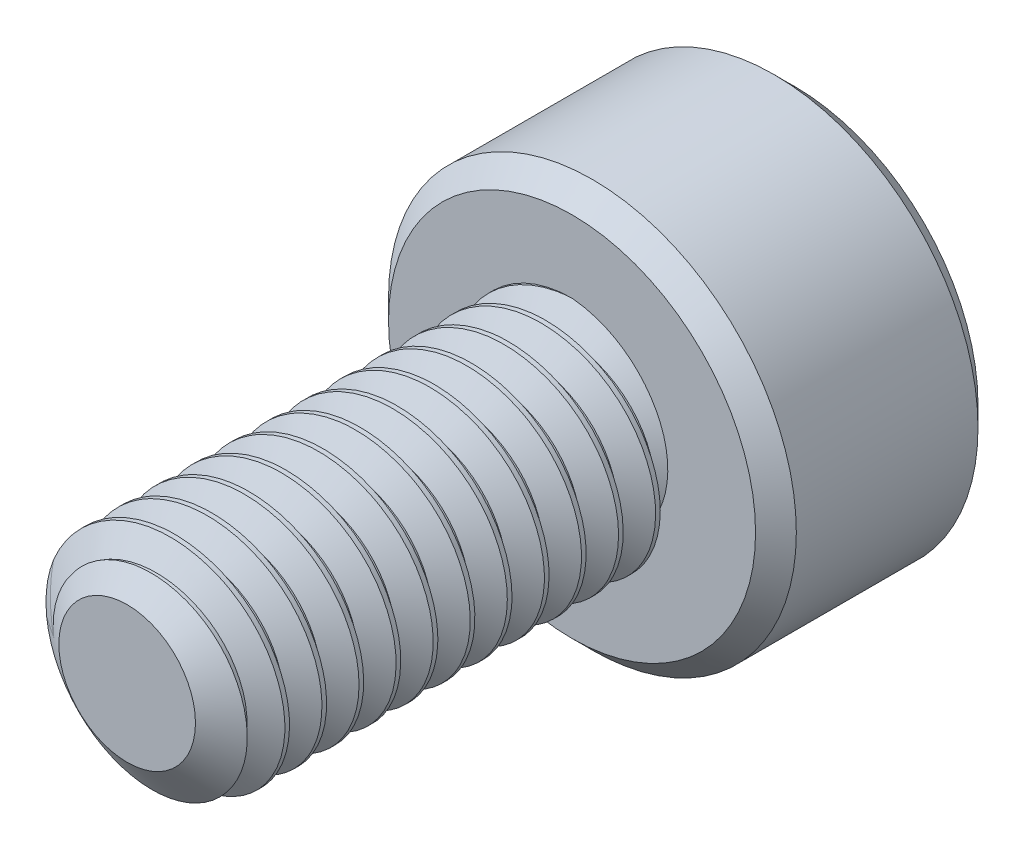
SolidWorks part; units mm, degrees
ref_plane "Front Plane" through (0, 0, 0) normal (0, 0, 1) x (1, 0, 0)
ref_plane "Top Plane" through (0, 0, 0) normal (0, 1, 0) x (1, 0, 0)
ref_plane "Right Plane" through (0, 0, 0) normal (1, 0, 0) x (0, 0, -1)
sketch "Sketch1" plane through (0, 0, 0) normal (0, 0, 1) x (1, 0, 0)
  circle A0 centre (0, 0) radius 1.5
  dimension "OD" = 3
extrude "Extrude1" add sketch "Sketch1" against normal blind 6
sketch "Sketch2" plane through (0, 0, 0) normal (0, 0, 1) x (1, 0, 0)
  circle A0 centre (0, 0) radius 1.5 construction
  circle A1 centre (0, 0) radius 1.5
curve "Helix/Spiral1" pitch 0.5 height 6.5 radius 1.5 centre (0, 0, 0) axis (0, 0, -1) start towards (0, 1, 0) parameters "pitch"=0.5
sketch "Sketch3" plane through (0, 0, 0) normal (1, 0, 0) x (0, 0, -1)
  line L0 (-0.4375, 1.5) -> (-0.25, 1.1752)
  line L1 (-0.25, 1.1752) -> (-0.1875, 1.1752)
  line L2 (-0.1875, 1.1752) -> (0, 1.5)
  line L3 (-0.4375, 1.5) -> (0, 1.5)
  line L4 (-0.2187, 1.5) -> (-0.2188, 1.1752) construction
  line L5 (-0.3438, 1.3376) -> (-0.0938, 1.3376) construction
  line L6 (0, 1.5) -> (0, -1.5) construction
  dimension "D1" = 0.0625
  dimension "D2" = 0.25
  dimension "D3" = 60
sweep "Cut-Sweep1" cut profiles "Sketch3" path "Helix/Spiral1" align with end faces yes
sketch "Sketch4" plane through (0, 0, 0) normal (1, 0, 0) x (0, 0, -1)
  line L0 (0.4053, 1.5) -> (0, 0.9212)
  line L1 (0, 0.9212) -> (0, 1.5)
  line L2 (0.4053, 1.5) -> (0, 1.5)
  line L3 (-0.4375, 1.5) -> (0, 1.5) construction
  line L4 (0, 0) -> (7.0209, 0) construction
  dimension "D1" = 55
  dimension "D2" = 0.254
revolve "Cut-Revolve1" cut sketch "Sketch4" angle 360 about L4
sketch "Sketch6" plane through (0, 0, -6) normal (0, 0, -1) x (-1, 0, 0)
  circle A0 centre (0, 0) radius 2.75
  dimension "head dia" = 5.5
extrude "Extrude2" add sketch "Sketch6" along normal blind 3
sketch "Sketch7" plane through (0, 0, -9) normal (0, 0, -1) x (-1, 0, 0)
  line L1 (0, 1.4434) -> (-1.25, 0.7217)
  line L2 (-1.25, 0.7217) -> (-1.25, -0.7217)
  line L3 (-1.25, -0.7217) -> (0, -1.4434)
  line L4 (0, -1.4434) -> (1.25, -0.7217)
  line L5 (1.25, -0.7217) -> (1.25, 0.7217)
  line L6 (1.25, 0.7217) -> (0, 1.4434)
  circle A0 centre (0, 0) radius 1.25 construction
  dimension "hex dia" = 2.5
extrude "Cut-Extrude1" cut sketch "Sketch7" against normal blind 1.875
sketch "Sketch8" plane through (0, 0, -9) normal (0, 0, -1) x (-1, 0, 0)
  circle A0 centre (0, 0) radius 1.4434
extrude "Cut-Extrude2" cut sketch "Sketch8" against normal through all draft 45
chamfer "Chamfer1" distance 0.275 angle 45 2 edges at (-2.75, 0, -9) (-2.75, 0, -6)
sketch "Sketch10" plane through (0, 0, -6) normal (0, 0, 1) x (1, 0, 0)
  circle A1 centre (0, 0) radius 1.5
  circle A2 centre (0, 0) radius 1.5
  dimension "D1" = 0
ref_plane "Plane1" through (0, 0, 0) normal (0, 0, 1) x (1, 0, 0)
extrude "partial thread" [suppressed] add sketch "Sketch10" along normal up to surface (4 mm away) separate body up to plane "Plane1"
chamfer "Chamfer2" [suppressed] distance 0.06 angle 45
combine bodies "Combine1" [suppressed] operation type add bodies to combine 107 108
sketch "Sketch9" plane through (0, 0, 0) normal (1, 0, 0) x (0, 0, -1)
  line L0 (0, 1.5) -> (0, -1.5) construction
  line L1 (1.25, 1.5) -> (1.25, -1.5) construction
  dimension "D1" = 1.25
equation "\"D3@Helix/Spiral1\" = \"screw length@Extrude1\"+\"pitch@Helix/Spiral1\""
equation "\"D1@Sketch3\" = \"pitch@Helix/Spiral1\"*.125"
equation "\"D2@Sketch3\" = \"pitch@Helix/Spiral1\"*.5"
equation "\"D1@Cut-Extrude1\" = \"hex dia@Sketch7\"*.75"
equation "\"D1@Chamfer1\" = \"head dia@Sketch6\"*.05"
equation "\"D1@Sketch9\" = \"pitch@Helix/Spiral1\"*2.5"
equation "\"D1@Chamfer2\"=\"OD@Sketch1\"*.02"
